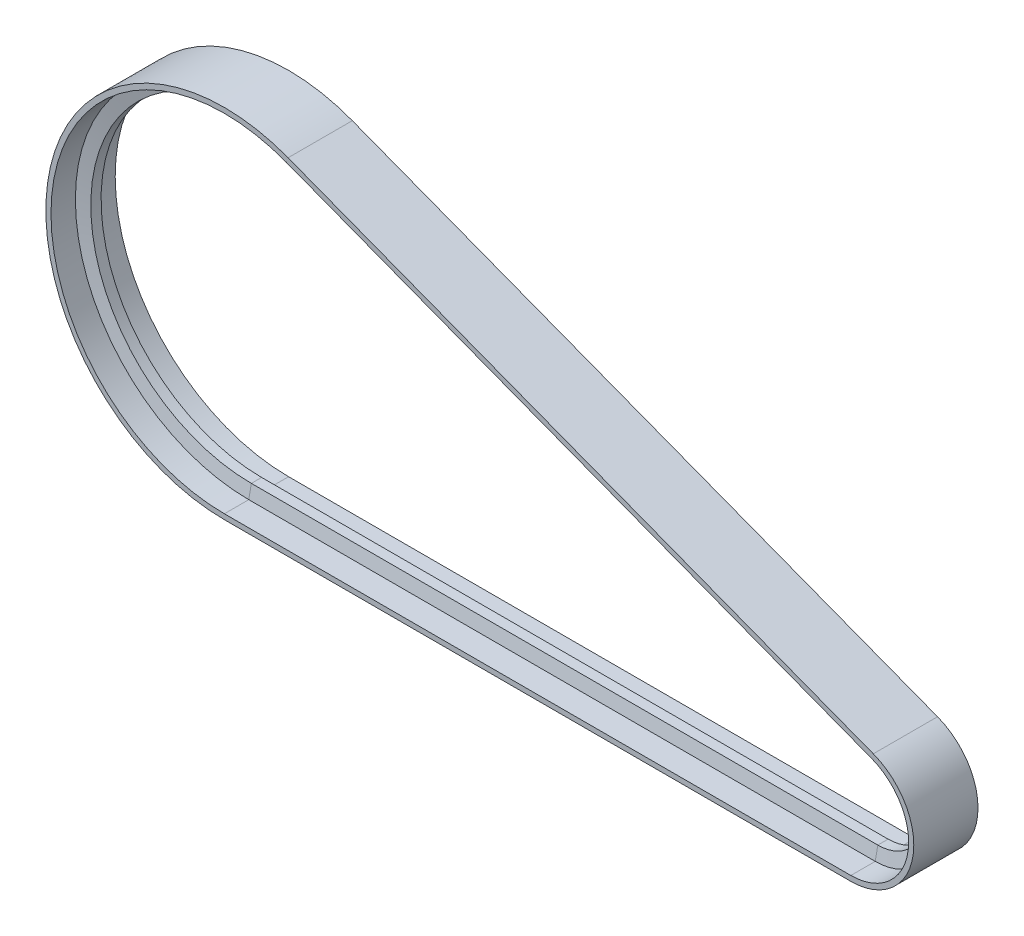
SolidWorks part; units mm, degrees
material "PBT General Purpose"
ref_plane "Front Plane" through (0, 0, 0) normal (0, 0, 1) x (1, 0, 0)
ref_plane "Top Plane" through (0, 0, 0) normal (0, 1, 0) x (1, 0, 0)
ref_plane "Right Plane" through (0, 0, 0) normal (1, 0, 0) x (0, 0, -1)
sketch "Sketch1" plane through (0, 0, 0) normal (0, 0, 1) x (1, 0, 0)
  line L0 (0, -67.5) -> (243.8832, -67.5)
  line L1 (24.0893, 63.0552) -> (251.9129, -23.9816)
  arc A0 (24.0893, 63.0552) -> (0, -67.5) centre (0, 0) ccw
  arc A1 (243.8832, -67.5) -> (251.9129, -23.9816) centre (243.8832, -45) ccw
  dimension "D1" = 45
  dimension "D2" = 135
  dimension "D3" = 248
extrude "Extrude-Thin1" add sketch "Sketch1" along normal mid plane 25 thin contours A0 L0 A1 L1 thin type one direction wall 2
sketch "Sketch2" plane through (0, 0, 0) normal (1, 0, 0) x (0, 0, -1)
  line L0 (-3, -67.5) -> (-2, -62.5)
  line L1 (-12.5, -67.5) -> (12.5, -67.5) construction
  line L2 (-2, -62.5) -> (2, -62.5)
  line L3 (2, -62.5) -> (3, -67.5)
  line L4 (0, -62.5) -> (0, -69.5) construction
  line L5 (-12.5, -69.5) -> (12.5, -69.5) construction
  line L6 (3, -67.5) -> (-3, -67.5)
  point P13 (0, -67.5)
  dimension "D1" = 6
  dimension "D2" = 4
  dimension "D3" = 5
sweep "Sweep1" add profiles "Sketch2" path "Sketch1<3>"
sketch "Sketch1<3>" plane through (0, 0, 0) normal (0, 0, 1) x (1, 0, 0) same geometry as "Sketch1"
move or copy body "Body-Move/Copy1" [suppressed] bodies to move or copy 102
